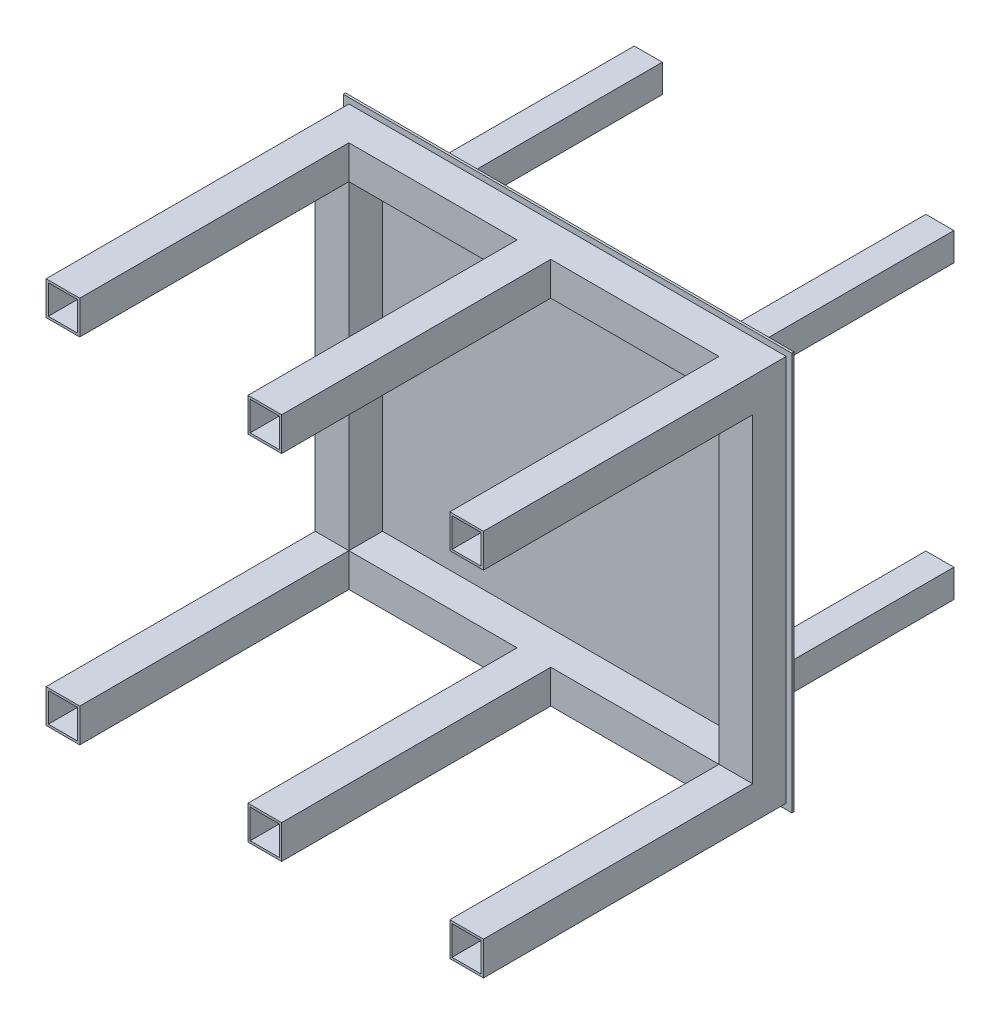
SolidWorks part; units mm, degrees
ref_plane "前基準面" through (0, 0, 0) normal (0, 0, 1) x (1, 0, 0)
ref_plane "上基準面" through (0, 0, 0) normal (0, 1, 0) x (1, 0, 0)
ref_plane "右基準面" through (0, 0, 0) normal (1, 0, 0) x (0, 0, -1)
sketch "草圖1" plane through (0, 0, 0) normal (0, 0, 1) x (1, 0, 0)
  line L0 (27.1343, 30.6601) -> (53.1343, 30.6601)
  line L1 (-159.8657, 37.6601) -> (240.1343, 37.6601)
  line L2 (-159.8657, 37.6601) -> (-159.8657, -317.3399)
  line L3 (-159.8657, -317.3399) -> (240.1343, -317.3399)
  line L4 (240.1343, 37.6601) -> (240.1343, -317.3399)
  line L5 (-152.8657, 30.6601) -> (-126.8657, 30.6601)
  line L6 (-152.8657, 30.6601) -> (-152.8657, 4.6601)
  line L7 (-152.8657, 4.6601) -> (-126.8657, 4.6601)
  line L8 (-126.8657, 30.6601) -> (-126.8657, 4.6601)
  line L9 (-154.8657, 32.6601) -> (-124.8657, 32.6601)
  line L10 (-154.8657, 32.6601) -> (-154.8657, 2.6601)
  line L11 (-154.8657, 2.6601) -> (-124.8657, 2.6601)
  line L12 (-124.8657, 32.6601) -> (-124.8657, 2.6601)
  line L13 (25.1343, 32.6601) -> (55.1343, 32.6601)
  line L14 (25.1343, 32.6601) -> (25.1343, 2.6601)
  line L15 (25.1343, 2.6601) -> (55.1343, 2.6601)
  line L16 (55.1343, 32.6601) -> (55.1343, 2.6601)
  line L17 (53.1343, 30.6601) -> (53.1343, 4.6601)
  line L18 (27.1343, 4.6601) -> (53.1343, 4.6601)
  line L19 (27.1343, 30.6601) -> (27.1343, 4.6601)
  line L20 (207.1343, 4.6601) -> (233.1343, 4.6601)
  line L21 (205.1343, 32.6601) -> (235.1343, 32.6601)
  line L22 (205.1343, 32.6601) -> (205.1343, 2.6601)
  line L23 (205.1343, 2.6601) -> (235.1343, 2.6601)
  line L24 (235.1343, 32.6601) -> (235.1343, 2.6601)
  line L25 (233.1343, 30.6601) -> (233.1343, 4.6601)
  line L26 (207.1343, 30.6601) -> (233.1343, 30.6601)
  line L27 (207.1343, 30.6601) -> (207.1343, 4.6601)
  line L28 (-152.8657, -284.3399) -> (-126.8657, -284.3399)
  line L29 (-154.8657, -282.3399) -> (-124.8657, -282.3399)
  line L30 (-154.8657, -282.3399) -> (-154.8657, -312.3399)
  line L31 (-154.8657, -312.3399) -> (-124.8657, -312.3399)
  line L32 (-124.8657, -282.3399) -> (-124.8657, -312.3399)
  line L33 (25.1343, -282.3399) -> (55.1343, -282.3399)
  line L34 (25.1343, -282.3399) -> (25.1343, -312.3399)
  line L35 (25.1343, -312.3399) -> (55.1343, -312.3399)
  line L36 (55.1343, -282.3399) -> (55.1343, -312.3399)
  line L37 (205.1343, -282.3399) -> (235.1343, -282.3399)
  line L38 (205.1343, -282.3399) -> (205.1343, -312.3399)
  line L39 (205.1343, -312.3399) -> (235.1343, -312.3399)
  line L40 (235.1343, -282.3399) -> (235.1343, -312.3399)
  line L41 (-126.8657, -284.3399) -> (-126.8657, -310.3399)
  line L42 (-152.8657, -310.3399) -> (-126.8657, -310.3399)
  line L43 (-152.8657, -284.3399) -> (-152.8657, -310.3399)
  line L44 (27.1343, -284.3399) -> (53.1343, -284.3399)
  line L45 (53.1343, -284.3399) -> (53.1343, -310.3399)
  line L46 (27.1343, -310.3399) -> (53.1343, -310.3399)
  line L47 (27.1343, -284.3399) -> (27.1343, -310.3399)
  line L48 (207.1343, -284.3399) -> (233.1343, -284.3399)
  line L49 (233.1343, -284.3399) -> (233.1343, -310.3399)
  line L50 (207.1343, -310.3399) -> (233.1343, -310.3399)
  line L51 (207.1343, -284.3399) -> (207.1343, -310.3399)
  point P52 (-139.8657, -312.3399)
  dimension "D1" = 400
  dimension "D2" = 355
  dimension "D3" = 30
  dimension "D4" = 30
  dimension "D5" = 26
  dimension "D6" = 26
  dimension "D7" = 2
  dimension "D8" = 2
  dimension "D9" = 30
  dimension "D10" = 30
  dimension "D12" = 30
  dimension "D13" = 30
  dimension "D15" = 150
  dimension "D16" = 150
  dimension "D17" = 5
  dimension "D18" = 0
  dimension "D19" = 0
  dimension "D20" = 30
  dimension "D21" = 30
  dimension "D23" = 30
  dimension "D24" = 30
  dimension "D26" = 30
  dimension "D27" = 30
  dimension "D29" = 285
  dimension "D30" = 0
  dimension "D31" = 0
  dimension "D32" = 5
  dimension "D33" = 150
  dimension "D34" = 150
  dimension "D35" = 0
  dimension "D11" = 2
  dimension "D14" = 2
  dimension "D22" = 2
  dimension "D25" = 2
  dimension "D28" = 2
extrude "填料-伸長1" add sketch "草圖1" along normal blind 270 contours L32 L31 L30 L29 | L42 L41 L28 L43 | L35 L36 L33 L34 | L46 L45 L44 L47 | L50 L49 L48 L51 | L39 L40 L37 L38 | L23 L24 L21 L22 | L20 L25 L26 L27 | L15 L16 L13 L14 | L18 L17 L0 L19 | L11 L12 L9 L10 | L7 L8 L5 L6
extrude "填料-伸長2" add sketch "草圖1<4>" against normal blind 2 contours L4 L3 L2 L1
sketch "草圖1<4>" plane through (0, 0, 0) normal (0, 0, 1) x (1, 0, 0) same geometry as "草圖1"
sketch "草圖3" plane through (0, 0, -2) normal (0, 0, -1) x (-1, 0, 0)
  line L0 (-181.1343, 1.1601) -> (-159.1343, 1.1601)
  line L1 (-182.6343, 2.6601) -> (-157.6343, 2.6601)
  line L2 (-182.6343, 2.6601) -> (-182.6343, -22.3399)
  line L3 (-182.6343, -22.3399) -> (-157.6343, -22.3399)
  line L4 (-157.6343, 2.6601) -> (-157.6343, -22.3399)
  line L5 (-159.1343, 1.1601) -> (-159.1343, -20.8399)
  line L6 (-181.1343, -20.8399) -> (-159.1343, -20.8399)
  line L7 (-181.1343, 1.1601) -> (-181.1343, -20.8399)
  line L9 (-240.1343, 37.6601) -> (-240.1343, -317.3399) construction
  line L10 (159.8657, 37.6601) -> (-240.1343, 37.6601) construction
  line L11 (-181.1343, -258.8399) -> (-159.1343, -258.8399)
  line L12 (-182.6343, -257.3399) -> (-157.6343, -257.3399)
  line L13 (-182.6343, -257.3399) -> (-182.6343, -282.3399)
  line L14 (-182.6343, -282.3399) -> (-157.6343, -282.3399)
  line L15 (-157.6343, -257.3399) -> (-157.6343, -282.3399)
  line L16 (-159.1343, -258.8399) -> (-159.1343, -280.8399)
  line L17 (-181.1343, -280.8399) -> (-159.1343, -280.8399)
  line L18 (-181.1343, -258.8399) -> (-181.1343, -280.8399)
  line L19 (159.8657, -317.3399) -> (-240.1343, -317.3399) construction
  line L20 (-40.1343, 37.6601) -> (-40.1343, -317.3399) construction
  line L21 (100.8657, -258.8399) -> (100.8657, -280.8399)
  line L22 (100.8657, -280.8399) -> (78.8657, -280.8399)
  line L23 (78.8657, -258.8399) -> (78.8657, -280.8399)
  line L24 (77.3657, -257.3399) -> (77.3657, -282.3399)
  line L25 (102.3657, -282.3399) -> (77.3657, -282.3399)
  line L26 (102.3657, -257.3399) -> (102.3657, -282.3399)
  line L27 (102.3657, -257.3399) -> (77.3657, -257.3399)
  line L28 (100.8657, -258.8399) -> (78.8657, -258.8399)
  line L29 (100.8657, 1.1601) -> (100.8657, -20.8399)
  line L30 (100.8657, -20.8399) -> (78.8657, -20.8399)
  line L31 (78.8657, 1.1601) -> (78.8657, -20.8399)
  line L32 (77.3657, 2.6601) -> (77.3657, -22.3399)
  line L33 (102.3657, -22.3399) -> (77.3657, -22.3399)
  line L34 (102.3657, 2.6601) -> (102.3657, -22.3399)
  line L35 (102.3657, 2.6601) -> (77.3657, 2.6601)
  line L36 (100.8657, 1.1601) -> (78.8657, 1.1601)
  point P12 (-182.6343, -9.8399)
  dimension "D1" = 25
  dimension "D2" = 25
  dimension "D4" = 57.5
  dimension "D5" = 35
  dimension "D6" = 25
  dimension "D7" = 25
  dimension "D9" = 57.5
  dimension "D10" = 35
  dimension "D3" = 1.5
  dimension "D8" = 1.5
extrude "填料-伸長3" add sketch "草圖3" along normal blind 200 contours L12 L15 L14 L13 | L11 L16 L17 L18 | L26 L25 L24 L27 | L21 L22 L23 L28 | L29 L30 L31 L36 | L34 L33 L32 L35 | L4 L3 L2 L1 | L5 L6 L7 L0
sketch "草圖8" plane through (-154.8657, 0, 0) normal (-1, 0, 0) x (0, 0, 1)
  line L0 (270, -312.3399) -> (0, -312.3399) construction
  line L1 (70, -312.3399) -> (100, -312.3399)
  line L2 (70, -312.3399) -> (70, -282.3399)
  line L3 (70, -282.3399) -> (100, -282.3399)
  line L4 (100, -312.3399) -> (100, -282.3399)
  line L5 (270, -282.3399) -> (0, -282.3399) construction
  line L6 (270, -282.3399) -> (270, -312.3399) construction
  line L7 (270, 2.6601) -> (0, 2.6601) construction
  line L8 (70, 2.6601) -> (100, 2.6601)
  line L9 (70, 2.6601) -> (70, 32.6601)
  line L10 (70, 32.6601) -> (100, 32.6601)
  line L11 (100, 2.6601) -> (100, 32.6601)
  line L12 (270, 32.6601) -> (0, 32.6601) construction
  line L14 (72, -310.3399) -> (98, -310.3399)
  line L15 (72, -310.3399) -> (72, -284.3399)
  line L16 (72, -284.3399) -> (98, -284.3399)
  line L17 (98, -310.3399) -> (98, -284.3399)
  line L18 (72, 4.6601) -> (98, 4.6601)
  line L19 (72, 4.6601) -> (72, 30.6601)
  line L20 (72, 30.6601) -> (98, 30.6601)
  line L21 (98, 4.6601) -> (98, 30.6601)
  dimension "D1" = 30
  dimension "D2" = 170
  dimension "D3" = 26
  dimension "D4" = 26
  dimension "D5" = 2
  dimension "D6" = 2
  dimension "D7" = 2
  dimension "D8" = 2
ref_plane "平面1" through (40.1343, 0, 0) normal (-1, 0, 0) x (0, 0, 1)
sketch "草圖9" plane through (0, -282.3399, 0) normal (0, 1, 0) x (1, 0, 0)
  line L0 (205.1343, -270) -> (205.1343, 0) construction
  line L1 (235.1343, 0) -> (205.1343, 0)
  line L2 (235.1343, 0) -> (235.1343, -30)
  line L3 (235.1343, -30) -> (205.1343, -30)
  line L4 (205.1343, 0) -> (205.1343, -30)
  dimension "D1" = 30
extrude "填料-伸長4" add sketch "草圖9" along normal blind 290
mirror "鏡射1" about plane through (40.1343, 0, 0) normal (-1, 0, 0) of "填料-伸長4"
sketch "草圖10" plane through (205.1343, 0, 0) normal (-1, 0, 0) x (0, 0, 1)
  line L1 (0, -312.3399) -> (30, -312.3399)
  line L2 (0, -312.3399) -> (0, -282.3399)
  line L3 (0, -282.3399) -> (30, -282.3399)
  line L4 (30, -312.3399) -> (30, -282.3399)
  line L5 (0, 32.6601) -> (30, 32.6601)
  line L6 (0, 32.6601) -> (0, 2.6601)
  line L7 (0, 2.6601) -> (30, 2.6601)
  line L8 (30, 32.6601) -> (30, 2.6601)
extrude "填料-伸長5" add sketch "草圖10" along normal blind 330
